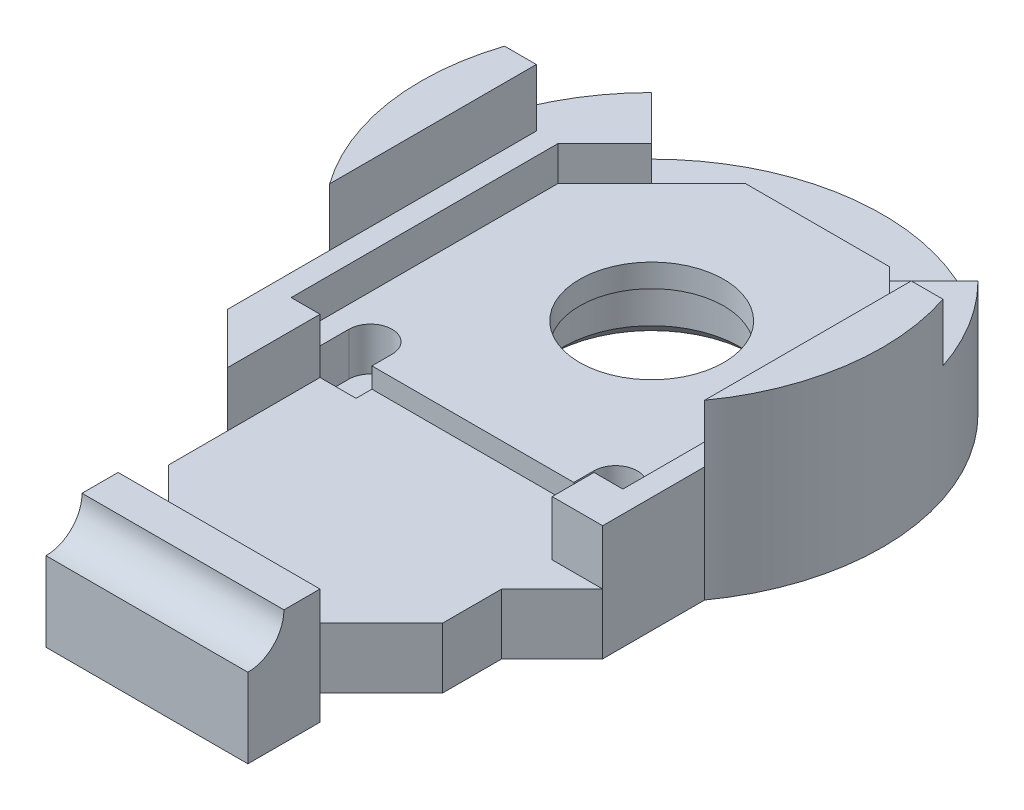
SolidWorks part; units mm, degrees
ref_plane "Front Plane" through (0, 0, 0) normal (0, 0, 1) x (1, 0, 0)
ref_plane "Top Plane" through (0, 0, 0) normal (0, 1, 0) x (1, 0, 0)
ref_plane "Right Plane" through (0, 0, 0) normal (1, 0, 0) x (0, 0, -1)
sketch "Sketch1" plane through (0, 0, 0) normal (0, 1, 0) x (1, 0, 0)
  line L0 (-1000.8836, -20) -> (48999.1164, -20) construction
  line L4 (6.5, -1010) -> (6.5, -4.6637) construction
  line L5 (6.5, -4.6637) -> (6.5, 4.6637) construction
  line L6 (-6.5, -1010) -> (-6.5, -4.6637) construction
  line L7 (6.5, -20) -> (6.5, -4.6637)
  line L8 (6.5, -20) -> (-6.5, -20)
  line L9 (-6.5, -20) -> (-6.5, -4.6637)
  line L10 (6.5, 4.6637) -> (6.5, 48990) construction
  line L11 (6.5, -4.6637) -> (6.5, 4.6637) construction
  line L12 (-6.5, -4.6637) -> (-6.5, 4.6637) construction
  line L13 (-6.5, -4.6637) -> (-6.5, 4.6637) construction
  line L14 (-6.5, 4.6637) -> (-6.5, 48990) construction
  arc A0 (6.5, 4.6637) -> (-6.5, 4.6637) centre (0, 0) ccw
  arc A1 (-8, 0) -> (-6.5, -4.6637) centre (0, 0) ccw
  arc A2 (-6.5, 4.6637) -> (-8, 0) centre (0, 0) ccw
  arc A3 (8, 0) -> (6.5, 4.6637) centre (0, 0) ccw
  arc A4 (-6.5, -4.6637) -> (6.5, -4.6637) centre (0, 0) ccw construction
  arc A5 (6.5, -4.6637) -> (8, 0) centre (0, 0) ccw
  dimension "D1" = 16
  dimension "D2" = 20
  dimension "D3" = 6.5
  dimension "D4" = 6.5
extrude "Boss-Extrude1" add sketch "Sketch1" along normal blind 4
sketch "Sketch2" plane through (0, 0, 0) normal (0, -1, 0) x (1, 0, 0)
  circle A0 centre (0, 0) radius 3.05
  dimension "D1" = 6.1
extrude "Cut-Extrude1" cut sketch "Sketch2" against normal blind 2
sketch "Sketch3" plane through (0, 2, 0) normal (0, -1, 0) x (1, 0, 0)
  circle A0 centre (0, 0) radius 1.5
  dimension "D1" = 3
extrude "Cut-Extrude2" cut sketch "Sketch3" against normal through all
sketch "Sketch5" plane through (0, 4, 0) normal (0, 1, 0) x (1, 0, 0)
  line L0 (-5.75, 0) -> (5.75, 0) construction
  line L1 (-5.75, -1000) -> (-5.75, -30) construction
  line L2 (5.75, -1000) -> (5.75, -30) construction
  line L3 (0, 0) -> (0, 5.75) construction
  line L4 (-1000, 5.75) -> (-0.75, 5.75) construction
  line L5 (2.5, 5.75) -> (0.75, 5.75)
  line L6 (-2.5, 5.75) -> (-5.75, 2.5)
  line L7 (-5.75, 2.5) -> (-5.75, -6.75)
  line L8 (2.5, 5.75) -> (5.75, 2.5)
  line L9 (5.75, 2.5) -> (5.75, -6.75)
  line L11 (-0.75, 5.75) -> (-0.75, 7.9648)
  line L12 (0.75, 5.75) -> (0.75, 7.9648)
  line L13 (-0.75, 5.75) -> (0, 5.75) construction
  line L14 (0.75, 5.75) -> (49000, 5.75) construction
  line L15 (0, 5.75) -> (-0.75, 5.75) construction
  line L16 (-0.75, 5.75) -> (-2.5, 5.75)
  line L17 (0.75, 5.75) -> (0, 5.75) construction
  line L18 (0, 5.75) -> (0.75, 5.75) construction
  line L20 (-5.75, -6.75) -> (-4.4, -6.75)
  line L21 (-5.5, -6.5) -> (5.5, -6.5) construction
  line L22 (-4.4, -6.75) -> (-4.4, -8.2)
  line L23 (-4.4, -28.5) -> (-4.4, -30) construction
  line L24 (4.4, -6.75) -> (4.4, -8.2)
  line L26 (-4.4, -6.75) -> (4.4, -6.75) construction
  line L27 (4.4, -6.75) -> (5.75, -6.75)
  line L28 (-2.9, -6.8941) -> (-2.9, -8.2) construction
  line L29 (2.9, -6.8941) -> (2.9, -8.2) construction
  line L30 (6.5, -15) -> (6.5, -20.6628) construction
  line L31 (-997.5796, -8.2) -> (49002.4204, -8.2) construction
  line L32 (2.9, -8.2) -> (2.1, -8.2) construction
  line L33 (4.4, -8.2) -> (5.66, -10) construction
  line L34 (-4.4, -8.2) -> (-5.66, -10)
  line L36 (-4.4, -8.2) -> (-4.4, -28.5) construction
  line L40 (4.4, -13.5) -> (4.4, -17.6628) construction
  line L41 (4.4, -8.2) -> (4.4, -13.5) construction
  line L43 (-6.5, -4.6637) -> (-6.5, -20) construction
  line L44 (6.5, -20) -> (6.5, -4.6637) construction
  line L45 (6.5, -11.2) -> (6.5, -15)
  line L47 (-6.5, -15) -> (-6.5, -11.2)
  line L49 (-6.5, -15) -> (6.5, -15)
  line L51 (-1005.75, 2.5) -> (48994.25, 2.5) construction
  line L52 (-6.5, -20.6628) -> (-6.5, -15) construction
  line L53 (-5.75, -19.937) -> (-5.75, -15) construction
  line L55 (-998.9168, -10) -> (49001.0832, -10) construction
  line L56 (5.66, -10) -> (6.5, -10) construction
  line L57 (6.5, -20.6628) -> (8.4925, -22.5911) construction
  line L58 (-6.5, -20.6628) -> (-8.4521, -22.5519) construction
  line L59 (6.5, -20) -> (6.5, -4.6637) construction
  line L60 (-5.75, -30) -> (-5.75, -19.937) construction
  line L61 (-5.75, -15) -> (-5.75, 49000) construction
  line L62 (6.5, -10) -> (6.5, -11.2)
  line L63 (5.75, -10.1286) -> (6.5, -11.2) construction
  line L64 (4.4, -17.6628) -> (4.4, -30) construction
  line L65 (5.75, -30) -> (5.75, -19.937) construction
  line L66 (5.75, -19.937) -> (5.75, 49000) construction
  line L67 (6.5, -20.6628) -> (6.5, -20) construction
  line L68 (5.66, -10) -> (5.75, -10.1286) construction
  line L69 (-5.66, -10) -> (-6.5, -10)
  line L70 (-6.5, -4.6637) -> (-6.5, -20) construction
  line L71 (-6.5, -10) -> (-6.5, -11.2)
  line L72 (-5.66, -10) -> (-5.75, -10.1286) construction
  line L73 (-5.75, -10.1286) -> (-6.5, -11.2)
  line L74 (4.4, -8.2) -> (6.5, -8.2)
  line L75 (6.5, -8.2) -> (6.5, -10)
  circle A0 centre (0, 0) radius 8 construction
  arc A2 (-0.75, 7.9648) -> (0.75, 7.9648) centre (0, 0) cw
  point P5 (0, 0)
  point P17 (0, 5.75)
  dimension "D1" = 5.75
  dimension "D2" = 0.75
  dimension "D3" = 0.75
  dimension "D4" = 11.5
  dimension "D5" = 0.25
  dimension "D6" = 1.5
  dimension "D7" = 1.5
  dimension "D8" = 3
  dimension "D9" = 3
  dimension "D10" = 2.5
  dimension "D11" = 10
  dimension "D12" = 15
extrude "Cut-Extrude4" cut sketch "Sketch5" against normal blind 1.2 contours L34 L69 L49 L56 L33 L24 L27 L9 L8 L5 L12 L11 L16 L6 L7 L20 L22 region at (0.0644, 4, 5.0846)
sketch "Sketch6" plane through (0, 2.8, 0) normal (0, 1, 0) x (1, 0, 0)
  circle A0 centre (0, 0) radius 2.5
  dimension "D1" = 5
sketch "Sketch7" plane through (0, 2.8, 0) normal (0, 1, 0) x (1, 0, 0)
  line L0 (-5, -5.5) -> (-5, -6.75)
  line L1 (-3.5, -5.5) -> (-3.5, -6.75)
  line L2 (3.5, -5.5) -> (3.5, -6.75)
  line L3 (5, -5.5) -> (5, -6.75)
  line L4 (4.4, -6.75) -> (5.75, -6.75) construction
  line L5 (3.5, -6.75) -> (5, -6.75)
  line L6 (-5.75, -6.75) -> (-4.4, -6.75) construction
  line L7 (-5, -6.75) -> (-3.5, -6.75)
  arc A0 (-3.5, -5.5) -> (-5, -5.5) centre (-4.25, -5.5) ccw
  arc A1 (5, -5.5) -> (3.5, -5.5) centre (4.25, -5.5) ccw
  arc A5 (-5, -5.5) -> (-3.5, -5.5) centre (-4.25, -5.5) ccw construction
  arc A6 (3.5, -5.5) -> (5, -5.5) centre (4.25, -5.5) ccw construction
  dimension "D1" = 1.5
  dimension "D2" = 1.5
extrude "Cut-Extrude6" cut sketch "Sketch7" against normal blind 1.5
sketch "Sketch9" plane through (0, 2.8, 0) normal (0, 1, 0) x (1, 0, 0)
  line L0 (-6.5, -15) -> (6.5, -15)
  line L1 (6.5, -15) -> (6.5, -11.2)
  line L5 (-6.5, -11.2) -> (-6.5, -15)
  line L6 (-4.4, -8.2) -> (-4.4, -6.2) construction
  line L7 (-6.5, -15) -> (6.5, -15) construction
  line L8 (4.4, -8.2) -> (4.4, -6.2) construction
  line L10 (4.4, -6.2) -> (-4.4, -6.2)
  line L11 (-4.75, -8.7) -> (-5.66, -10)
  line L12 (6.5, -11.2) -> (6.5, -10)
  line L13 (6.5, -15) -> (6.5, -8.2) construction
  line L15 (5.66, -10) -> (6.5, -11.2) construction
  line L17 (4.4, -8.2) -> (6.5, -8.2) construction
  line L18 (-4.4, -8.2) -> (-5.66, -10) construction
  line L19 (-6.5, -10) -> (-6.5, -15) construction
  line L20 (-6.5, -10) -> (-6.5, -11.2)
  line L21 (-6.5, -10) -> (-5.66, -10)
  line L22 (-5.66, -10) -> (-6.5, -11.2) construction
  line L23 (-4.4, -6.2) -> (-4.75, -6.2)
  line L24 (-4.75, -6.2) -> (-4.75, -8.7)
  line L25 (4.4, -6.75) -> (4.4, -8.2) construction
  line L26 (-4.4, -8.2) -> (-4.75, -8.7) construction
  line L27 (4.4, -6.2) -> (4.75, -6.2)
  line L28 (4.75, -6.2) -> (4.75, -8.2)
  line L29 (4.4, -8.2) -> (4.75, -8.2) construction
  line L30 (4.75, -8.2) -> (6.5, -8.2)
  line L31 (6.5, -8.2) -> (6.5, -10)
  dimension "D1" = 2
  dimension "D2" = 0.35
  dimension "D3" = 0.35
extrude "Cut-Extrude7" cut sketch "Sketch9" against normal blind 0.7
sketch "Sketch11" plane through (0, 0, 20) normal (0, 0, 1) x (1, 0, 0)
  line L0 (-6.5, 4) -> (-6.5, 0) construction
  line L1 (-6.5, 4) -> (6.5, 4)
  line L2 (-6.5, 4) -> (-6.5, 0)
  line L3 (-6.5, 0) -> (6.5, 0)
  line L4 (6.5, 4) -> (6.5, 0)
  line L5 (-6.5, 4) -> (6.5, 4) construction
extrude "Cut-Extrude9" [suppressed] cut sketch "Sketch11" against normal up to vertex up to point (4.4, 3.05, 8.2)
sketch "Sketch14" plane through (0, 4, 0) normal (0, 1, 0) x (1, 0, 0)
  line L0 (6.5, -4.6637) -> (6.5, 2.5)
  line L1 (-6.5, -4.6637) -> (-6.5, 2.5)
  line L2 (-1005.75, 2.5) -> (48994.25, 2.5) construction
  line L3 (-6.5, 2.5) -> (-7.5993, 2.5)
  line L4 (6.5, 2.5) -> (7.5993, 2.5)
  line L5 (-6.5, 2.5) -> (-6.5, 4.6637) construction
  line L6 (6.5, 2.5) -> (6.5, 4.6637) construction
  arc A0 (6.5, -4.6637) -> (0.75, 7.9648) centre (0, 0) ccw construction
  arc A1 (-0.75, 7.9648) -> (-6.5, -4.6637) centre (0, 0) ccw construction
  arc A2 (6.5, -4.6637) -> (7.5993, 2.5) centre (0, 0) ccw
  arc A3 (-6.5, -4.6637) -> (-7.5993, 2.5) centre (0, 0) cw
  arc A4 (-7.5993, 2.5) -> (-6.5, 4.6637) centre (0, 0) cw construction
  arc A5 (7.5993, 2.5) -> (6.5, 4.6637) centre (0, 0) ccw construction
  dimension "D1" = 8
  dimension "D2" = 8
extrude "Boss-Extrude3" add sketch "Sketch14" along normal blind 2
sketch "Sketch15" plane through (0, 4, 0) normal (0, 1, 0) x (1, 0, 0)
  line L0 (2.5, 5.75) -> (-2.5, 5.75)
  line L3 (0, 0) -> (35355.3391, 35355.3391) construction
  line L4 (5.75, 2.5) -> (2.5, 5.75) construction
  line L5 (0, 0) -> (-35355.3391, 35355.3391) construction
  line L6 (-2.5, 5.75) -> (-5.75, 2.5) construction
  line L7 (2.5, 5.75) -> (4.125, 4.125)
  line L8 (4.125, 4.125) -> (5.6569, 5.6569)
  line L9 (-2.5, 5.75) -> (-4.125, 4.125)
  line L10 (-4.125, 4.125) -> (-5.6569, 5.6569)
  arc A0 (-0.75, 7.9648) -> (-7.5993, 2.5) centre (0, 0) ccw construction
  arc A1 (7.5993, 2.5) -> (0.75, 7.9648) centre (0, 0) ccw construction
  arc A2 (5.6569, 5.6569) -> (-5.6569, 5.6569) centre (0, 0) ccw
  point P18 (4.125, 4.125)
  point P23 (-4.125, 4.125)
extrude "Cut-Extrude12" cut sketch "Sketch15" against normal blind 2
extrude "Cut-Extrude13" cut sketch "Sketch6" against normal through all
sketch "Sketch17" plane through (0, 4, 0) normal (0, 1, 0) x (1, 0, 0)
  line L0 (-4.75, -6.75) -> (-4.4, -6.75)
  line L1 (-4.4, -6.75) -> (-4.4, -8.2)
  line L2 (-4.4, -8.2) -> (-4.75, -8.7)
  line L3 (-4.75, -8.7) -> (-4.75, -6.75)
  line L4 (4.4, -6.75) -> (4.75, -6.75)
  line L5 (4.75, -6.75) -> (4.75, -8.2)
  line L6 (4.75, -8.2) -> (4.4, -8.2)
  line L7 (4.4, -8.2) -> (4.4, -6.75)
  line L8 (4.4, -8.2) -> (6.5, -8.2) construction
extrude "Cut-Extrude14" cut sketch "Sketch17" against normal up to surface (1.9 mm away) up to face at (-0.4354, 2.1, 8.8077)
sketch "Sketch18" plane through (0, 2.1, 0) normal (0, 1, 0) x (1, 0, 0)
  line L0 (-6.5, -10) -> (-6.5, -15)
  line L1 (-6.5, -10) -> (-5.66, -10)
  line L2 (-5.66, -10) -> (-4.75, -8.7)
  line L3 (-4.75, -8.7) -> (-4.75, -15)
  line L4 (-6.5, -15) -> (6.5, -15) construction
  line L5 (-4.75, -15) -> (-6.5, -15)
extrude "Boss-Extrude5" add sketch "Sketch18" along normal up to surface (1.9 mm away) up to face at (-5.7933, 4, 2.6789)
sketch "Sketch19" plane through (0, 4, 0) normal (0, 1, 0) x (1, 0, 0)
  line L0 (-6.5, -20) -> (-3.5, -20)
  line L1 (-6.5, -20) -> (6.5, -20) construction
  line L2 (-3.5, -20) -> (-3.5, -15)
  line L3 (-4.75, -15) -> (6.5, -15) construction
  line L4 (-3.5, -15) -> (-4.75, -15)
  line L5 (-4.75, -15) -> (-4.75, -8.2)
  line L6 (-4.75, -6.75) -> (-4.75, -15) construction
  line L7 (-4.75, -8.2) -> (-6.5, -8.2)
  line L8 (-6.5, -4.6637) -> (-6.5, -20) construction
  line L9 (-6.5, -8.2) -> (-6.5, -20)
  line L10 (4.75, -8.2) -> (6.5, -8.2) construction
  line L11 (0, -3.3) -> (0, 3.3) construction
  line L12 (4.75, -8.2) -> (6.5, -8.2)
  line L13 (4.75, -15) -> (4.75, -8.2)
  line L14 (3.5, -15) -> (4.75, -15)
  line L15 (3.5, -20) -> (3.5, -15)
  line L16 (6.5, -20) -> (3.5, -20)
  line L17 (6.5, -8.2) -> (6.5, -20)
  dimension "D1" = 3
extrude "Cut-Extrude15" cut sketch "Sketch19" against normal through all both and the other way through all
sketch "Sketch20" plane through (0, 2.1, 0) normal (0, 1, 0) x (1, 0, 0)
  line L0 (4.75, -15) -> (1.75, -15)
  line L1 (-3.5, -15) -> (3.5, -15) construction
  line L2 (1.75, -15) -> (4.75, -12)
  line L3 (4.75, -8.2) -> (4.75, -15) construction
  line L4 (4.75, -12) -> (4.75, -15)
  line L5 (-4.75, -15) -> (-1.75, -15)
  line L6 (-3.5, -15) -> (3.5, -15) construction
  line L7 (-1.75, -15) -> (-4.75, -12)
  line L8 (-4.75, -8.2) -> (-4.75, -15) construction
  line L9 (-4.75, -12) -> (-4.75, -15)
  dimension "D1" = 3
  dimension "D2" = 3
  dimension "D3" = 45
  dimension "D4" = 45
extrude "Cut-Extrude16" cut sketch "Sketch20" against normal through all both and the other way through all
sketch "Sketch21" plane through (3.5, 0, 0) normal (1, 0, 0) x (0, 0, -1)
  line L0 (-15, 4) -> (-20, 4) construction
  line L1 (-18.75, 4) -> (-16.25, 4)
  arc A0 (-18.75, 4) -> (-16.25, 4) centre (-17.5, 4) ccw
  arc A1 (-16.25, 4) -> (-18.75, 4) centre (-17.5, 4) ccw construction
  dimension "D1" = 2.5
extrude "Cut-Extrude17" cut sketch "Sketch21" against normal through all both and the other way through all
chamfer "Chamfer1" distance 1.75 angle 45 2 edges at (4.75, 1.05, 8.2) (-4.75, 1.05, 8.2)
sketch "Sketch22" plane through (3.5, 0, 0) normal (1, 0, 0) x (0, 0, -1)
  line L1 (-20, 0) -> (-17.5, 0)
  line L2 (-20, 0) -> (-20, 2.75)
  line L3 (-20, 2.75) -> (-17.5, 2.75) construction
  line L4 (-17.5, 0) -> (-17.5, 2.75)
  line L5 (-18.75, 4) -> (-20, 4)
  line L6 (-18.75, 4) -> (-18.75, 2.75) construction
  line L7 (-18.75, 2.75) -> (-20, 2.75) construction
  line L8 (-20, 4) -> (-20, 2.75)
  arc A0 (-18.75, 4) -> (-16.25, 4) centre (-17.5, 4) ccw construction
  arc A1 (-17.5, 2.75) -> (-18.75, 4) centre (-17.5, 4) cw
extrude "Cut-Extrude18" cut sketch "Sketch22" against normal through all contours L4 region at (3.5, 1.7944, 18.8506)
sketch "Sketch23" plane through (0, 0, 0) normal (0, -1, 0) x (1, 0, 0)
  line L0 (-3.5, 13.25) -> (-3.5, 10.2905)
  line L1 (-1.75, 15) -> (-4.75, 12) construction
  line L2 (-3.5, 13.25) -> (-6.5, 13.25)
  line L3 (-6.5, 13.25) -> (-6.5, 6.006)
  line L4 (-6.5, 6.006) -> (-3.5, 10.2905)
  line L5 (-3.5, 17.5) -> (-3.5, 15) construction
  line L6 (-6.5, 4.6637) -> (-6.5, 8.2) construction
  dimension "D1" = 35
  dimension "D2" = 8.85
extrude "Cut-Extrude19" [suppressed] cut sketch "Sketch23" against normal through all
sketch "Sketch24" plane through (0, 2.1, 0) normal (0, 1, 0) x (1, 0, 0)
  line L0 (-6.5, -8.2) -> (-4.75, -8.2)
  line L1 (-4.75, -8.2) -> (-4.75, -9.95)
  line L2 (-4.75, -9.95) -> (-6.5, -8.2)
extrude "Boss-Extrude6" add sketch "Sketch24" along normal up to surface (1.9 mm away) up to face at (5.8067, 4, 1.7168)
chamfer "Chamfer2" distance 0.5 angle 45 1 edges at (0, 0, -3.05)
